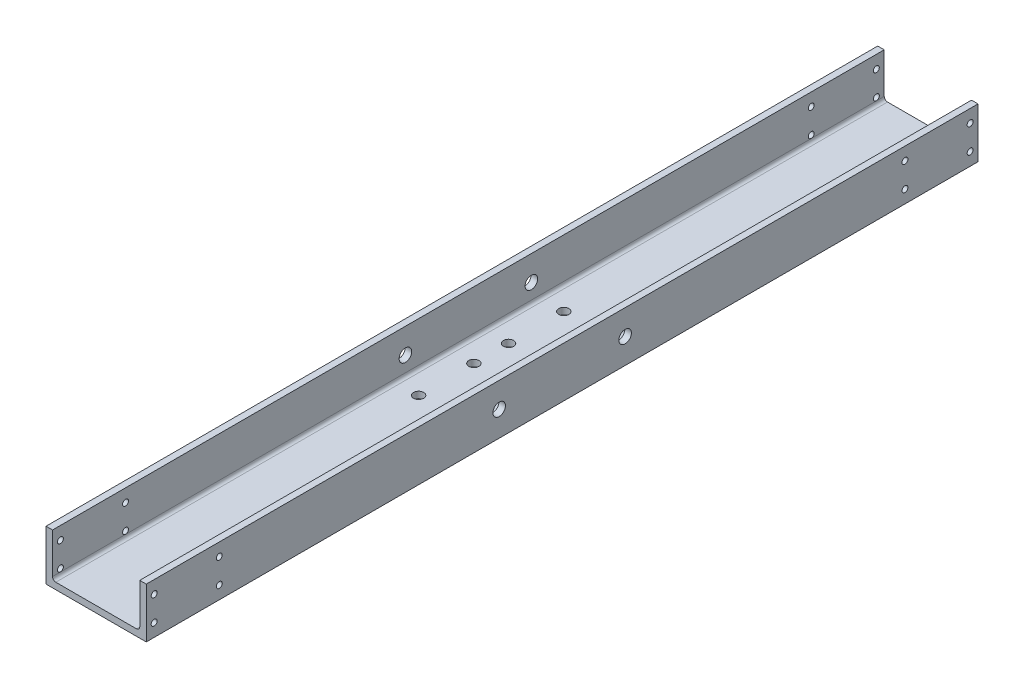
SolidWorks part; units mm, degrees
ref_plane "Front Plane" through (0, 0, 0) normal (0, 0, 1) x (1, 0, 0)
ref_plane "Top Plane" through (0, 0, 0) normal (0, 1, 0) x (1, 0, 0)
ref_plane "Right Plane" through (0, 0, 0) normal (1, 0, 0) x (0, 0, -1)
sketch "Sketch1" plane through (0, 0, 0) normal (0, 0, 1) x (1, 0, 0)
  line L0 (-25.4, 12.7) -> (-25.4, -12.7) construction
  line L1 (-25.4, -12.7) -> (25.4, -12.7) construction
  line L2 (25.4, -12.7) -> (25.4, 12.7) construction
  line L3 (22.098, -9.398) -> (-22.098, -9.398) construction
  line L4 (-22.098, -9.398) -> (-22.098, 12.7) construction
  line L6 (-22.098, 12.7) -> (-25.4, 12.7) construction
  line L7 (0, -12.7) -> (0, 0) construction
  line L8 (25.4, 12.7) -> (22.098, 12.7) construction
  line L9 (22.098, 12.7) -> (22.098, -9.398) construction
  line L10 (0, -9.398) -> (0, -12.7) construction
  point P4 (0, 0)
  point P11 (25.4, -9.398)
  dimension "Outside Height" = 25.4
  dimension "Outside Width" = 50.8
  dimension "Leg Thickness" = 3.302
  dimension "D1" = 12.7
  dimension "Inside Height" = 22.098
  dimension "Inside Width" = 44.196
  dimension "Base Thickness" = 3.302
sketch "Sketch2" plane through (0, 0, 0) normal (1, 0, 0) x (0, 0, -1)
  line L0 (210.695, 12.7) -> (-210.695, 12.7) construction
  line L1 (0, -9.398) -> (0, 12.7) construction
  point P0 (-159.895, 12.7)
  point P4 (0, 12.7)
  point P6 (159.895, 12.7)
  dimension "D1" = 50.8
  dimension "D2" = 50.8
  dimension "Length" = 421.39
sketch "Sketch3" plane through (0, 0, 0) normal (0, 0, 1) x (1, 0, 0)
  line L6 (-25.4, 12.7) -> (-25.4, -12.7)
  line L7 (-25.4, -12.7) -> (25.4, -12.7)
  line L8 (25.4, -12.7) -> (25.4, 12.7)
  line L9 (25.4, 12.7) -> (22.098, 12.7)
  line L10 (22.098, 12.7) -> (22.098, -9.398)
  line L11 (22.098, -9.398) -> (-22.098, -9.398)
  line L12 (-22.098, -9.398) -> (-22.098, 12.7)
  line L13 (-22.098, 12.7) -> (-25.4, 12.7)
extrude "Boss-Extrude1" add sketch "Sketch3" along normal mid plane 421.39
fillet "Fillet1" radius 1.651 2 edges at (22.098, -9.398, 0) (-22.098, -9.398, 0)
sketch "Sketch4" plane through (0, -9.398, 0) normal (0, 1, 0) x (1, 0, 0)
  line L0 (0, 210.695) -> (0, -210.695) construction
  line L1 (20.447, 210.695) -> (-20.447, 210.695) construction
  line L2 (20.447, -210.695) -> (-20.447, -210.695) construction
  line L3 (-23.5304, 0) -> (23.5304, 0) construction
  circle A0 centre (-10.5304, 8.79) radius 2.585
  circle A1 centre (10.4696, 8.79) radius 2.585
  circle A2 centre (-10.5304, 36.79) radius 2.585
  circle A3 centre (10.4696, 36.79) radius 2.585
  circle A4 centre (-10.5304, -36.79) radius 2.585
  circle A5 centre (10.4696, -36.79) radius 2.585
  circle A6 centre (10.4696, -8.79) radius 2.585
  circle A7 centre (-10.5304, -8.79) radius 2.585
  point P24 (0, 0)
  point P26 (0, 0)
  dimension "D1" = 5.17
  dimension "D2" = 5.17
  dimension "D3" = 28
  dimension "D4" = 8.79
  dimension "D5" = 8.79
  dimension "D6" = 28
extrude "Cut-Extrude1" cut sketch "Sketch4" against normal blind 10
sketch "Sketch9" plane through (0, 0, 0) normal (1, 0, 0) x (0, 0, -1)
  line L0 (0, 0) -> (0, -12.7) construction
  line L1 (-210.695, -12.7) -> (210.695, -12.7) construction
  line L2 (0, 0) -> (-95.1707, 0) construction
  circle A0 centre (-31.91, 0) radius 3.18
  circle A1 centre (31.91, 0) radius 3.18
  dimension "D2" = 6.36
  dimension "D1" = 31.91
extrude "Cut-Extrude2" cut sketch "Sketch9" against normal mid plane 60
sketch "Sketch10" plane through (0, 0, 0) normal (1, 0, 0) x (0, 0, -1)
  line L0 (0, 0) -> (0, 12.7) construction
  line L2 (-210.695, 0) -> (210.695, 0) construction
  line L3 (-210.695, -12.7) -> (-210.695, 12.7) construction
  line L4 (210.695, -12.7) -> (210.695, 12.7) construction
  line L5 (-206.695, -6.2) -> (-206.695, 6.2) construction
  line L7 (-206.695, 6.2) -> (-169.6086, 6.2) construction
  line L8 (206.695, 6.2) -> (169.6086, 6.2) construction
  line L9 (206.695, -6.2) -> (206.695, 6.2) construction
  circle A0 centre (-206.695, 6.2) radius 1.5
  circle A1 centre (-206.695, -6.2) radius 1.5
  circle A2 centre (-173.695, 6.2) radius 1.5
  circle A3 centre (-173.695, -6.2) radius 1.5
  circle A4 centre (173.695, 6.2) radius 1.5
  circle A5 centre (173.695, -6.2) radius 1.5
  circle A6 centre (206.695, -6.2) radius 1.5
  circle A7 centre (206.695, 6.2) radius 1.5
  point P13 (-206.695, 0)
  dimension "D3" = 3
  dimension "D1" = 4
  dimension "D2" = 33
extrude "Cut-Extrude3" cut sketch "Sketch10" against normal mid plane 60
equation "\"D1@Boss-Extrude1\"=\"Length@Sketch2\""
equation "\"D2@Sketch2\"=\"D1@Sketch2\""
equation "\"D1@Sketch1\"=\"Outside Height@Sketch1\"/2"
equation "\"D1@Fillet1\"=\"Leg Thickness@Sketch1\"*.5"
equation "\"D1@Sketch2\"=\"Outside Width@Sketch1\"*1"
